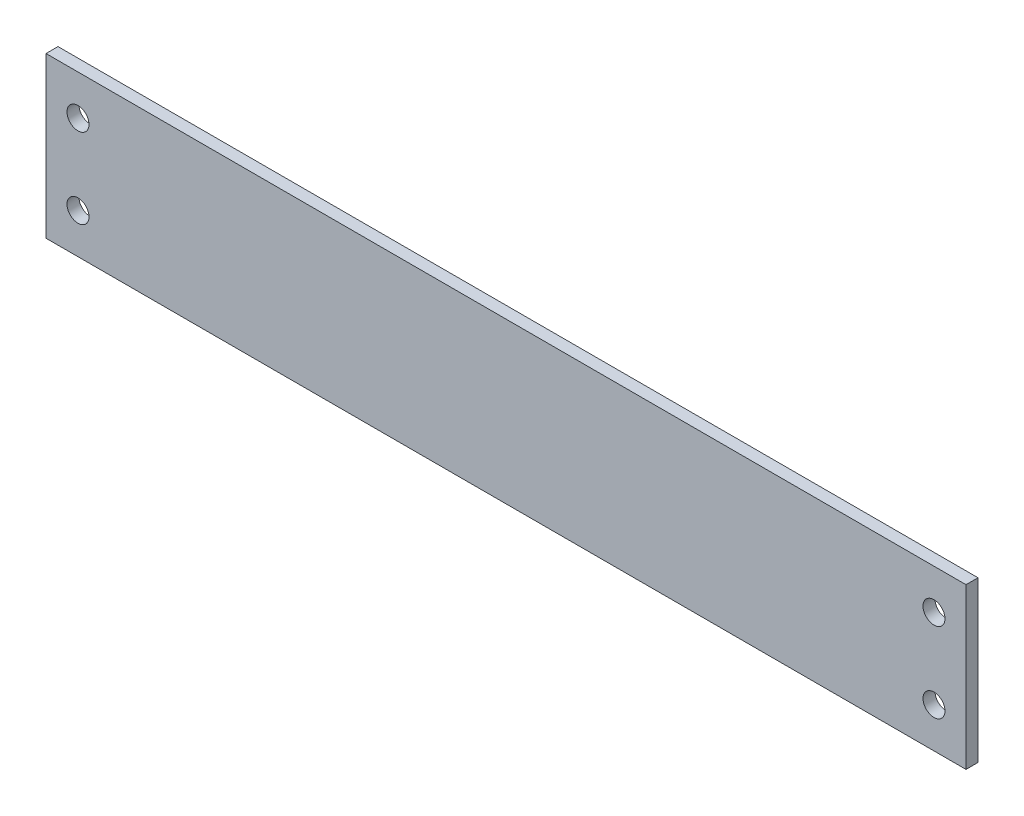
SolidWorks part; units mm, degrees
ref_plane "Front Plane" through (0, 0, 0) normal (0, 0, 1) x (1, 0, 0)
ref_plane "Top Plane" through (0, 0, 0) normal (0, 1, 0) x (1, 0, 0)
ref_plane "Right Plane" through (0, 0, 0) normal (1, 0, 0) x (0, 0, -1)
sketch "Extrusion Base Sketch" plane through (0, 0, 0) normal (0, 0, 1) x (1, 0, 0)
  line L0 (208.75, 36.75) -> (208.75, -3.25)
  line L1 (0, 0) -> (187.5, 0) construction
  line L2 (0, 0) -> (0, 33.5) construction
  line L3 (0, 33.5) -> (187.5, 33.5) construction
  line L4 (187.5, 0) -> (187.5, 33.5) construction
  line L5 (-21.25, 36.75) -> (208.75, 36.75)
  line L6 (-3.25, 36.75) -> (-3.25, -3.25) construction
  line L7 (-21.25, -3.25) -> (208.75, -3.25)
  line L8 (190.75, 36.75) -> (190.75, -3.25) construction
  line L9 (-21.25, 36.75) -> (-21.25, -3.25)
  line L10 (200.75, 26.75) -> (200.75, 6.75) construction
  line L11 (200.75, 16.75) -> (208.75, 16.75) construction
  line L12 (-13.25, 26.75) -> (-13.25, 6.75) construction
  line L13 (-13.25, 16.75) -> (-21.25, 16.75) construction
  dimension "D1" = 33.5
  dimension "D2" = 187.5
  dimension "D4" = 3.25
  dimension "D5" = 3.25
  dimension "D6" = 3.25
  dimension "D3" = 40
  dimension "D7" = 230
extrude "Extrusion Base Extrude" add sketch "Extrusion Base Sketch" against normal blind 3
hole_wizard "M5 Mounting Holes" positions "M5 Mounting Holes Position Sketch" profile "M5 Mounting Holes Profile Sketch" hole size "M5" standard "ANSI Metric" end condition through all
sketch "M5 Mounting Holes Position Sketch" plane through (0, 0, -3) normal (0, 0, -1) x (-1, 0, 0)
  point P0 (-200.75, 26.75)
  point P2 (-200.75, 6.75)
  point P4 (13.25, 26.75)
  point P6 (13.25, 6.75)
sketch "M5 Mounting Holes Profile Sketch" plane through (200.75, 26.75, -3) normal (1, 0, 0) x (0, 1, 0)
  line L0 (0, 0) -> (0, 3)
  line L1 (0, 3) -> (2.75, 3)
  line L2 (2.75, 3) -> (2.75, 0)
  line L5 (2.75, 0) -> (0, 0)
  line L11 (0, -6.35) -> (0, 107.95) construction
  dimension "Thru Hole Dia." = 5.5
  dimension "Thru Hole Depth" = 3
equation "\"Logo Height\"= 33.5mm"
equation "\"Total Height\"= 40mm"
equation "\"Border\"= ( \"Total Height\" - \"Logo Height\" ) / 2"
equation "\"Logo Length\"= 187.5mm"
equation "\"D1@Extrusion Base Sketch\" = \"Logo Height\""
equation "\"D2@Extrusion Base Sketch\" = \"Logo Length\""
equation "\"D4@Extrusion Base Sketch\" = \"Border\""
equation "\"D5@Extrusion Base Sketch\" = \"Border\""
equation "\"D6@Extrusion Base Sketch\" = \"Border\""
equation "\"D3@Extrusion Base Sketch\" = \"Total Height\""
